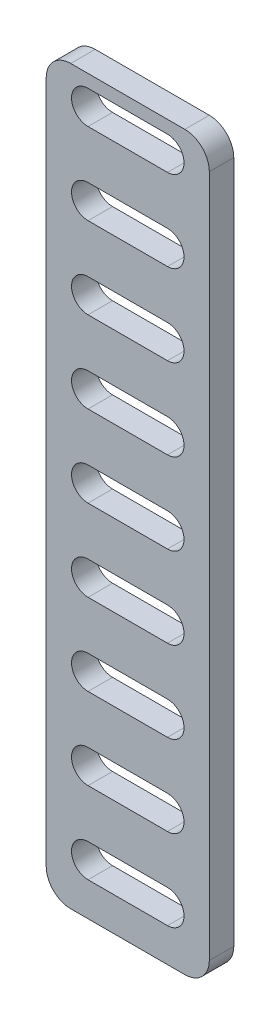
SolidWorks part; units mm, degrees
material "Alloy Steel"
ref_plane "Front Plane" through (0, 0, 0) normal (0, 0, 1) x (1, 0, 0)
ref_plane "Top Plane" through (0, 0, 0) normal (0, 1, 0) x (1, 0, 0)
ref_plane "Right Plane" through (0, 0, 0) normal (1, 0, 0) x (0, 0, -1)
sketch "Sketch1" plane through (0, 0, 0) normal (0, 0, 1) x (1, 0, 0)
  line L6 (-81.0668, 33.9086) -> (-101.0668, 33.9086)
  line L7 (-81.0668, 123.6866) -> (-101.0668, 123.6866)
  line L8 (-91.0668, 24.5794) -> (-91.0668, 142.0861) construction
  line L9 (-86.196, 40.0812) -> (-95.9377, 40.0812) construction
  line L10 (-101.0668, 123.6866) -> (-101.0668, 33.9086)
  line L11 (-81.0668, 123.6866) -> (-81.0668, 33.9086)
  line L12 (-86.196, 38.0536) -> (-95.9377, 38.0536)
  line L13 (-86.196, 42.1089) -> (-95.9377, 42.1089)
  line L14 (-86.196, 50.0812) -> (-95.9377, 50.0812) construction
  line L15 (-86.196, 48.0536) -> (-95.9377, 48.0536)
  line L16 (-86.196, 52.1089) -> (-95.9377, 52.1089)
  line L17 (-86.196, 60.0812) -> (-95.9377, 60.0812) construction
  line L20 (-86.196, 58.0536) -> (-95.9377, 58.0536)
  line L23 (-86.196, 62.1089) -> (-95.9377, 62.1089)
  line L26 (-86.196, 70.0812) -> (-95.9377, 70.0812) construction
  line L29 (-86.196, 68.0536) -> (-95.9377, 68.0536)
  line L32 (-86.196, 72.1089) -> (-95.9377, 72.1089)
  line L35 (-86.196, 80.0812) -> (-95.9377, 80.0812) construction
  line L38 (-86.196, 78.0536) -> (-95.9377, 78.0536)
  line L39 (-86.196, 82.1089) -> (-95.9377, 82.1089)
  line L40 (-86.196, 90.0812) -> (-95.9377, 90.0812) construction
  line L41 (-86.196, 88.0536) -> (-95.9377, 88.0536)
  line L42 (-86.196, 92.1089) -> (-95.9377, 92.1089)
  line L43 (-86.196, 100.0812) -> (-95.9377, 100.0812) construction
  line L44 (-86.196, 98.0536) -> (-95.9377, 98.0536)
  line L45 (-86.196, 102.1089) -> (-95.9377, 102.1089)
  line L46 (-86.196, 110.0812) -> (-95.9377, 110.0812) construction
  line L47 (-86.196, 108.0536) -> (-95.9377, 108.0536)
  line L48 (-86.196, 112.1089) -> (-95.9377, 112.1089)
  line L49 (-86.196, 120.0812) -> (-95.9377, 120.0812) construction
  line L50 (-86.196, 118.0536) -> (-95.9377, 118.0536)
  line L51 (-86.196, 122.1089) -> (-95.9377, 122.1089)
  line L52 (-81.0668, 123.6866) -> (-78.0668, 123.6866) construction
  arc A0 (-86.196, 38.0536) -> (-86.196, 42.1089) centre (-86.196, 40.0812) ccw
  arc A1 (-95.9377, 42.1089) -> (-95.9377, 38.0536) centre (-95.9377, 40.0812) ccw
  arc A2 (-86.196, 48.0536) -> (-86.196, 52.1089) centre (-86.196, 50.0812) ccw
  arc A3 (-95.9377, 52.1089) -> (-95.9377, 48.0536) centre (-95.9377, 50.0812) ccw
  arc A18 (-86.196, 58.0536) -> (-86.196, 62.1089) centre (-86.196, 60.0812) ccw
  arc A19 (-95.9377, 62.1089) -> (-95.9377, 58.0536) centre (-95.9377, 60.0812) ccw
  arc A20 (-86.196, 68.0536) -> (-86.196, 72.1089) centre (-86.196, 70.0812) ccw
  arc A21 (-95.9377, 72.1089) -> (-95.9377, 68.0536) centre (-95.9377, 70.0812) ccw
  arc A22 (-86.196, 78.0536) -> (-86.196, 82.1089) centre (-86.196, 80.0812) ccw
  arc A23 (-95.9377, 82.1089) -> (-95.9377, 78.0536) centre (-95.9377, 80.0812) ccw
  arc A24 (-86.196, 88.0536) -> (-86.196, 92.1089) centre (-86.196, 90.0812) ccw
  arc A25 (-95.9377, 92.1089) -> (-95.9377, 88.0536) centre (-95.9377, 90.0812) ccw
  arc A26 (-86.196, 98.0536) -> (-86.196, 102.1089) centre (-86.196, 100.0812) ccw
  arc A27 (-95.9377, 102.1089) -> (-95.9377, 98.0536) centre (-95.9377, 100.0812) ccw
  arc A28 (-86.196, 108.0536) -> (-86.196, 112.1089) centre (-86.196, 110.0812) ccw
  arc A29 (-95.9377, 112.1089) -> (-95.9377, 108.0536) centre (-95.9377, 110.0812) ccw
  arc A30 (-86.196, 118.0536) -> (-86.196, 122.1089) centre (-86.196, 120.0812) ccw
  arc A31 (-95.9377, 122.1089) -> (-95.9377, 118.0536) centre (-95.9377, 120.0812) ccw
  point P8 (-91.0668, 40.0812)
  point P15 (-91.0668, 50.0812)
  point P23 (-91.0668, 60.0812)
  point P30 (-91.0668, 70.0812)
  point P37 (-91.0668, 80.0812)
  point P44 (-91.0668, 90.0812)
  point P51 (-91.0668, 100.0812)
  point P58 (-91.0668, 110.0812)
  point P65 (-91.0668, 120.0812)
  dimension "D1" = 10
  dimension "D3" = 20
  dimension "D4" = 10
  dimension "D2" = 8
extrude "Boss-Extrude1" add sketch "Sketch1" along normal blind 3
fillet "Fillet1" radius 3 4 edges at (-101.0668, 123.6866, 1.5) (-81.0668, 123.6866, 1.5) (-101.0668, 33.9086, 1.5) (-81.0668, 33.9086, 1.5)
